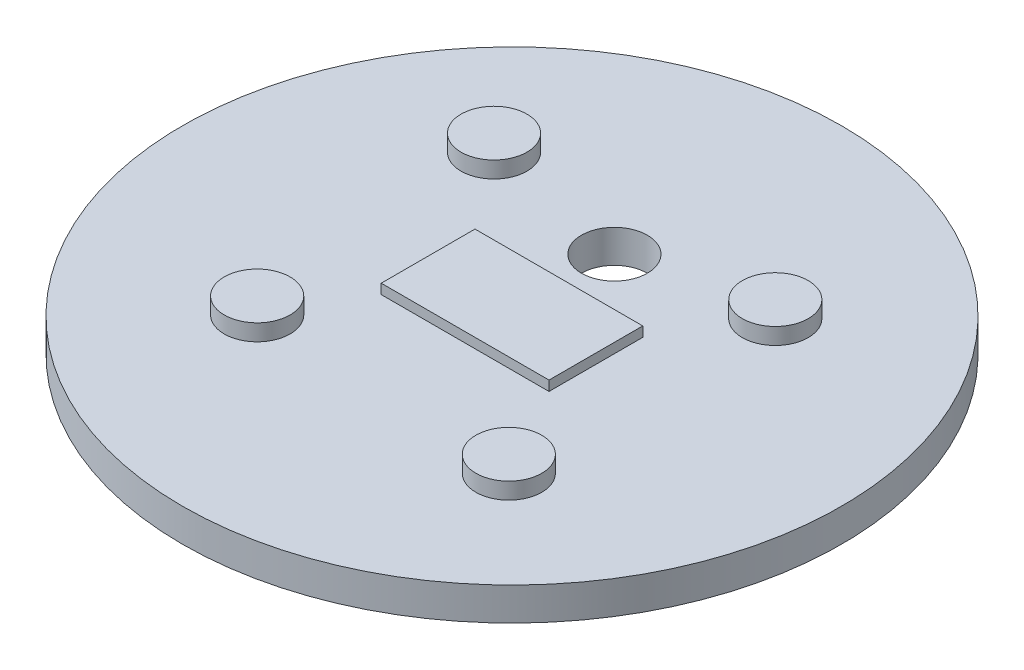
SolidWorks part; units mm, degrees
ref_plane "前视基准面" through (0, 0, 0) normal (0, 0, 1) x (1, 0, 0)
ref_plane "上视基准面" through (0, 0, 0) normal (0, 1, 0) x (1, 0, 0)
ref_plane "右视基准面" through (0, 0, 0) normal (1, 0, 0) x (0, 0, -1)
sketch "草图1" plane through (0, 0, 0) normal (0, 1, 0) x (1, 0, 0)
  circle A0 centre (0, 0) radius 100
  dimension "D1" = 200
extrude "凸台-拉伸1" add sketch "草图1" against normal blind 10
sketch "草图3" plane through (0, 0, 0) normal (0, 1, 0) x (1, 0, 0)
  line L1 (-25.4543, 14.2245) -> (25.4543, 14.2245)
  line L2 (-25.4543, 14.2245) -> (-25.4543, -14.2245)
  line L3 (-25.4543, -14.2245) -> (25.4543, -14.2245)
  line L4 (25.4543, 14.2245) -> (25.4543, -14.2245)
  line L5 (-25.4543, 14.2245) -> (25.4543, -14.2245) construction
  line L6 (-25.4543, -14.2245) -> (25.4543, 14.2245) construction
  point P0 (0, 0)
extrude "凸台-拉伸2" add sketch "草图3" along normal blind 3
sketch "草图4" plane through (0, 0, 0) normal (0, 1, 0) x (1, 0, 0)
  circle A0 centre (-0.695, 31.7644) radius 10
  dimension "D1" = 20
extrude "切除-拉伸1" cut sketch "草图4" against normal blind 13
sketch "草图5" plane through (0, 0, 0) normal (0, 1, 0) x (1, 0, 0)
  circle A1 centre (40.8553, -41.8178) radius 10
  circle A2 centre (-38.9302, -38.3954) radius 10
  circle A5 centre (-45.775, 40.3205) radius 10
  circle A6 centre (40.6414, 39.251) radius 10
  point P0 (40.8553, -41.8178)
  point P8 (-30.8019, 64.0637)
  point P11 (32.5131, 64.0637)
  point P14 (65.2401, 29.1976)
  point P15 (0, 0)
  point P18 (-63.315, 27.0586)
  point P21 (0, -68.1278)
  point P22 (-59.8926, -28.5559)
  point P23 (0, 0)
  point P24 (0, 0)
extrude "凸台-拉伸3" add sketch "草图5" along normal blind 5
